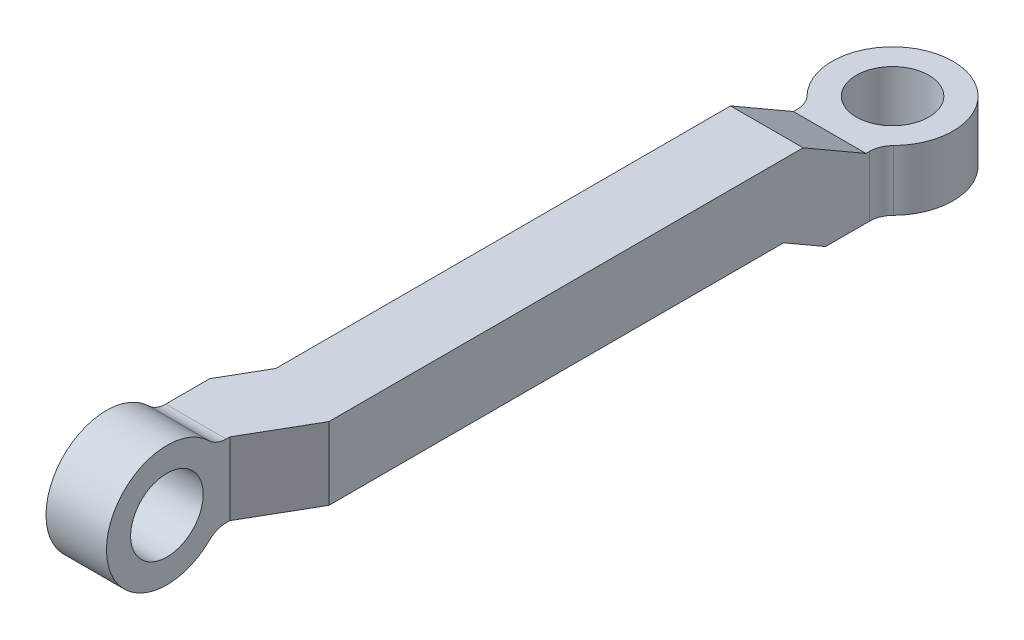
SolidWorks part; units mm, degrees
ref_plane "Front Plane" through (0, 0, 0) normal (0, 0, 1) x (1, 0, 0)
ref_plane "Top Plane" through (0, 0, 0) normal (0, 1, 0) x (1, 0, 0)
ref_plane "Right Plane" through (0, 0, 0) normal (1, 0, 0) x (0, 0, -1)
sketch "Sketch1" plane through (0, 0, 0) normal (1, 0, 0) x (0, 0, -1)
  line L0 (1370, 0) -> (1625, 0)
  line L1 (1286.5064, -125) -> (1625, -125)
  line L2 (1625, 0) -> (1625, -125)
  line L3 (1500, 114.3572) -> (1500, -244.7915) construction
  line L4 (100, 75) -> (1240.0962, 75)
  line L5 (100, -75) -> (1199.9038, -75)
  line L6 (1199.9038, -75) -> (1286.5064, -125)
  line L7 (1240.0962, 75) -> (1370, 0)
  line L8 (0, 0) -> (311.6739, 0) construction
  circle A0 centre (0, 0) radius 125
  circle A1 centre (0, 0) radius 75
  dimension "D1" = 250
  dimension "D2" = 150
  dimension "D3" = 125
  dimension "D4" = 1500
  dimension "D5" = 150
  dimension "D6" = 150
  dimension "D7" = 130
  dimension "D8" = 30
extrude "Boss-Extrude1" add sketch "Sketch1" against normal blind 125 contours A0 A1 region at (0, 38.4104, -115.2313)
extrude "Boss-Extrude2" add sketch "Sketch1<3>" along normal mid plane 250 contours L3 L0 A0 L1 | L0 L3 L1 L2 region at (0, -9.1174, -801.6003) region at (0, -62.5, -1562.5)
sketch "Sketch1<3>" plane through (0, 0, 0) normal (1, 0, 0) x (0, 0, -1) same geometry as "Sketch1"
fillet "Fillet1" 2 edges at (125, -62.5, -1625) (-125, -62.5, -1625) type full round first side face at (125, -31.25, -1071.4383) second side face at (-125, 0, -75) middle face at (0, -62.5, -1625)
sketch "Sketch2" plane through (0, 0, 0) normal (0, 1, 0) x (1, 0, 0)
  circle A0 centre (0, 1500) radius 75
  dimension "D1" = 150
extrude "Cut-Extrude1" cut sketch "Sketch2" against normal through all both and the other way through all
ref_plane "Plane1" through (0, 0, -300) normal (0, 0, 1) x (1, 0, 0)
sketch "Sketch4" plane through (0, 0, 0) normal (0, 1, 0) x (1, 0, 0)
  line L0 (0, 0) -> (0, 130)
  line L1 (0, 130) -> (75, 259.9038)
  line L2 (-279.4063, -53.9459) -> (-75, 300.0962)
  line L3 (75, 259.9038) -> (75, 1400)
  line L4 (125, 100) -> (125, 1240.0962) construction
  line L5 (-75, 1400) -> (-75, 300.0962)
  line L6 (0, 1500) -> (0, 1193.7779) construction
  arc A0 (125, 1500) -> (-125, 1500) centre (0, 1500) ccw construction
  arc A1 (75, 1400) -> (-75, 1400) centre (0, 1500) ccw
  dimension "D1" = 30
  dimension "D2" = 150
  dimension "D3" = 150
  dimension "D4" = 130
split "Split2" trim tools "Sketch4" bodies to split 103 resulting bodies 108
fillet "Fillet2" radius 50 4 edges at (-62.5, -75, -100) (-62.5, 75, -100) (-75, -62.5, -1400) (75, -62.5, -1400)
